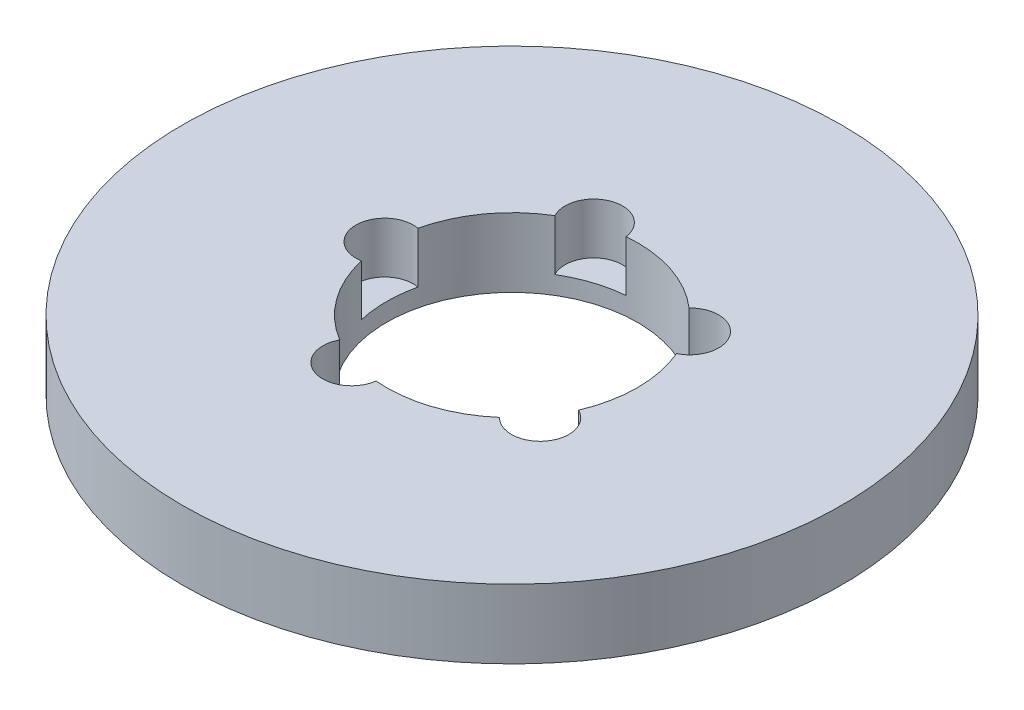
SolidWorks part; units mm, degrees
ref_plane "Front Plane" through (0, 0, 0) normal (0, 0, 1) x (1, 0, 0)
ref_plane "Top Plane" through (0, 0, 0) normal (0, 1, 0) x (1, 0, 0)
ref_plane "Right Plane" through (0, 0, 0) normal (1, 0, 0) x (0, 0, -1)
sketch "Sketch1" plane through (0, 0, 0) normal (0, 1, 0) x (1, 0, 0)
  circle A0 centre (0, 0) radius 52.5
  dimension "FLANGE_OD" = 105
extrude "Boss-Extrude1" add sketch "Sketch1" along normal blind 11
sketch "Sketch2" plane through (0, 0, 0) normal (0, 1, 0) x (1, 0, 0)
  circle A0 centre (0, 0) radius 20
  dimension "BORE_D" = 40
extrude "Cut-Extrude1" cut sketch "Sketch2" along normal through all
sketch "Sketch3" plane through (0, 11, 0) normal (0, 1, 0) x (1, 0, 0)
  circle A0 centre (0, 0) radius 20.2924 construction
  circle A1 centre (-20.2924, 0) radius 4.5759
  dimension "BOLT_D" = 9.1518
  dimension "BOLT_PCD" = 40.5848
extrude "Cut-Extrude2" cut sketch "Sketch3" against normal blind 8.1232
pattern_circular "CirPattern1" count 5 over 360 about axis through (0, 0, 0) along (0, 1, 0) of "Cut-Extrude2"
